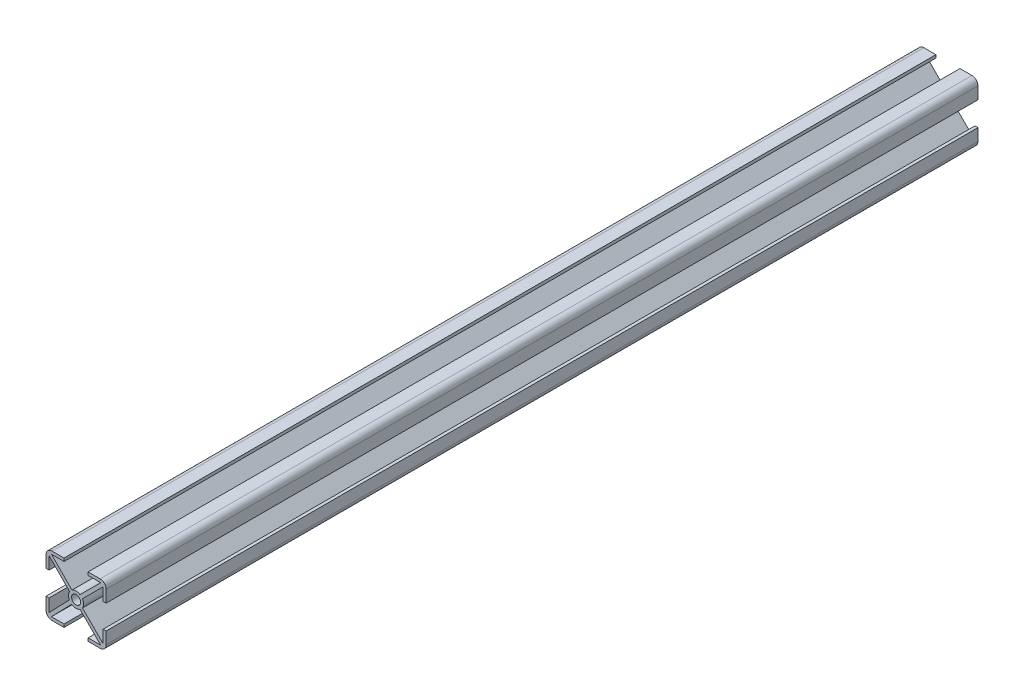
SolidWorks part; units mm, degrees
ref_plane "Plan de face" through (0, 0, 0) normal (0, 0, 1) x (1, 0, 0)
ref_plane "Plan de dessus" through (0, 0, 0) normal (0, 1, 0) x (1, 0, 0)
ref_plane "Plan de droite" through (0, 0, 0) normal (1, 0, 0) x (0, 0, -1)
sketch "Esquisse1" plane through (0, 0, 0) normal (0, 0, 1) x (1, 0, 0)
  line L0 (-19, 18.2) -> (-12.144, 11.2858)
  line L1 (0, 0) -> (-20, 0)
  line L2 (0, 0) -> (0, 20)
  line L3 (0, 20) -> (-20, 20)
  line L4 (-20, 0) -> (-20, 20)
  line L6 (-19, 18.2) -> (-19, 1.8)
  line L7 (-18.2, 1) -> (-1.8, 1)
  line L8 (-1, 18.2) -> (-1, 1.8)
  line L9 (-11.3575, 12.0994) -> (-18.2, 19)
  line L10 (-19, 1.8) -> (-12.2027, 8.8177)
  line L11 (-18.2, 1) -> (-11.4531, 7.9657)
  line L12 (-8.6781, 7.8781) -> (-1.8, 1)
  line L13 (-7.8781, 8.6781) -> (-1, 1.8)
  line L14 (-8.6781, 12.1219) -> (-1.8, 19)
  line L15 (-7.8781, 11.3219) -> (-1, 18.2)
  line L16 (-18.2, 19) -> (-1.8, 19)
  circle A0 centre (-10, 10) radius 1.5
  arc A1 (-8.6781, 12.1219) -> (-11.3575, 12.0994) centre (-10, 10) ccw
  arc A2 (-7.8781, 8.6781) -> (-7.8781, 11.3219) centre (-10, 10) ccw
  arc A3 (-11.4531, 7.9657) -> (-8.6781, 7.8781) centre (-10, 10) ccw
  arc A4 (-12.144, 11.2858) -> (-12.2027, 8.8177) centre (-10, 10) ccw
  dimension "D3" = 3
  dimension "D10" = 5
  dimension "D1" = 20
  dimension "D2" = 20
  dimension "D4" = 10
  dimension "D5" = 10
  dimension "D6" = 16.4
  dimension "D7" = 1
  dimension "D8" = 1
  dimension "D9" = 1
  dimension "D11" = 9
  dimension "D12" = 9.718
  dimension "D13" = 1.1316
  dimension "D14" = 9.7371
  dimension "D15" = 9.7699
  dimension "D16" = 1.1312
  dimension "D17" = 9.6975
  dimension "D18" = 9.7271
  dimension "D19" = 1.1314
  dimension "D20" = 9.7271
  dimension "D21" = 9.7271
  dimension "D22" = 1.1314
extrude "Boss.-Extru.1" add sketch "Esquisse1" along normal blind 290
fillet "Congé1" radius 2 4 edges at (0, 0, 145) (-20, 0, 145) (-20, 20, 145) (0, 20, 145)
sketch "Esquisse2" plane through (0, 0, 290) normal (0, 0, 1) x (1, 0, 0)
  line L0 (-2, 20) -> (-18, 20) construction
  line L1 (-14, 20) -> (-6, 20)
  line L2 (-14, 20) -> (-14, 19)
  line L3 (-14, 19) -> (-6, 19)
  line L4 (-6, 20) -> (-6, 19)
  line L5 (-20, 14) -> (-19, 14)
  line L6 (-20, 14) -> (-20, 6)
  line L7 (-20, 6) -> (-19, 6)
  line L8 (-19, 14) -> (-19, 6)
  line L9 (-14, 1) -> (-6, 1)
  line L10 (-14, 1) -> (-14, 0)
  line L11 (-14, 0) -> (-6, 0)
  line L12 (-6, 1) -> (-6, 0)
  line L13 (-1, 14) -> (0, 14)
  line L14 (-1, 14) -> (-1, 6)
  line L15 (-1, 6) -> (0, 6)
  line L16 (0, 14) -> (0, 6)
  line L17 (-18, 0) -> (-2, 0) construction
  line L18 (-20, 18) -> (-20, 2) construction
  line L19 (-19, 18.2) -> (-19, 1.8) construction
  line L20 (0, 2) -> (0, 18) construction
  line L21 (-1.8, 19) -> (-18.2, 19) construction
  line L22 (-1, 1.8) -> (-1, 18.2) construction
  line L23 (-18.2, 1) -> (-1.8, 1) construction
  dimension "D1" = 6
  dimension "D2" = 6
  dimension "D3" = 0
  dimension "D4" = 0
  dimension "D5" = 6
  dimension "D6" = 6
  dimension "D7" = 0
  dimension "D8" = 0
  dimension "D9" = 6
  dimension "D10" = 6
  dimension "D11" = 0
  dimension "D12" = 0
  dimension "D13" = 0
  dimension "D14" = 0
  dimension "D15" = 6
  dimension "D16" = 6
extrude "Enlèv. mat.-Extru.1" cut sketch "Esquisse2" against normal through all
